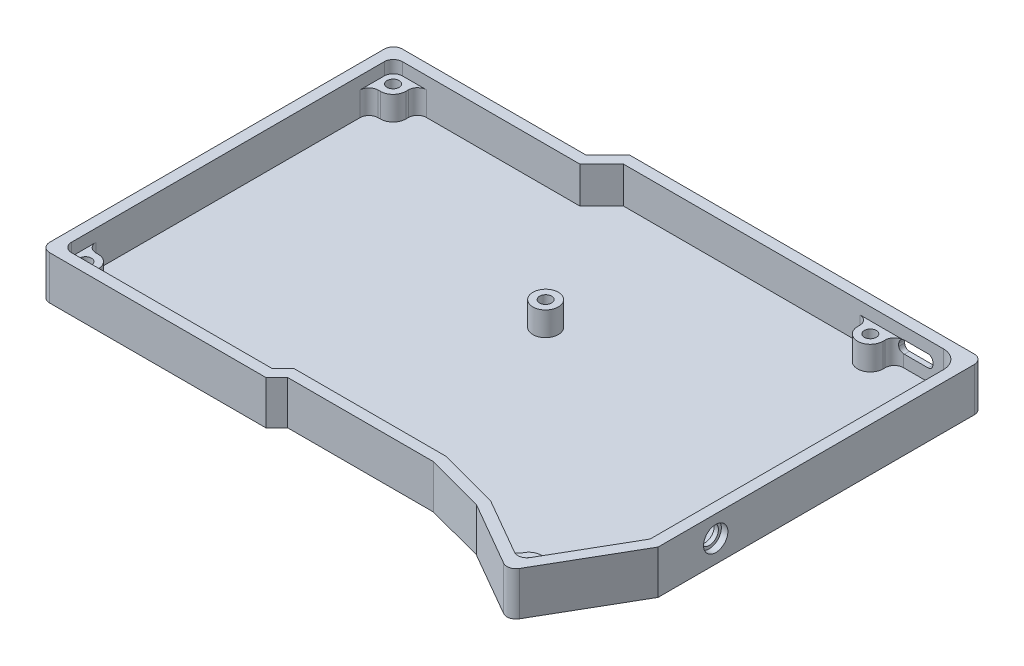
SolidWorks part; units mm, degrees
ref_plane "Front Plane" through (0, 0, 0) normal (0, 0, 1) x (1, 0, 0)
ref_plane "Top Plane" through (0, 0, 0) normal (0, 1, 0) x (1, 0, 0)
ref_plane "Right Plane" through (0, 0, 0) normal (1, 0, 0) x (0, 0, -1)
sketch "Sketch1" plane through (0, 0, 0) normal (0, 1, 0) x (1, 0, 0)
  line L0 (74.625, 48) -> (-17.625, 48) construction
  line L1 (-74.625, -48) -> (74.625, -48) construction
  line L2 (-74.625, -48) -> (-74.625, 48) construction
  line L3 (-74.625, 48) -> (74.625, 48) construction
  line L4 (74.625, -48) -> (74.625, 48) construction
  line L5 (-74.625, -48) -> (74.625, 48) construction
  line L6 (-74.625, 48) -> (74.625, -48) construction
  line L7 (-17.625, 48) -> (-17.625, 42) construction
  line L8 (-17.625, 42) -> (-23.625, 42) construction
  line L9 (-17.625, 48) -> (-23.625, 42) construction
  line L10 (-23.625, 42) -> (-74.625, 42) construction
  line L11 (-74.625, 42) -> (-74.625, -48) construction
  line L12 (-74.625, -48) -> (-17.625, -48) construction
  line L13 (-17.625, -48) -> (-17.625, -45) construction
  line L14 (-17.625, -45) -> (-14.625, -45) construction
  line L15 (-14.625, -45) -> (-17.625, -48) construction
  line L16 (-14.625, -45) -> (27.375, -45) construction
  line L17 (74.625, 48) -> (74.625, -37) construction
  line L18 (27.375, -45) -> (44.3045, -45) construction
  line L19 (44.3045, -45) -> (44.3045, -49.5167) construction
  line L20 (44.3045, -49.5167) -> (27.375, -45) construction
  line L21 (44.3045, -49.5167) -> (61.6269, -49.5167) construction
  line L22 (61.6269, -49.5167) -> (61.6269, -59.5048) construction
  line L23 (44.3045, -49.5167) -> (61.6269, -59.5048) construction
  line L24 (74.625, -37) -> (61.6269, -59.5048) construction
  line L25 (75.125, -37.134) -> (61.81, -60.1875)
  line L26 (44.1119, -49.9828) -> (61.81, -60.1875)
  line L27 (44.1119, -49.9828) -> (27.3094, -45.5)
  line L28 (-14.4179, -45.5) -> (27.3094, -45.5)
  line L29 (-14.4179, -45.5) -> (-17.4179, -48.5)
  line L30 (-75.125, -48.5) -> (-17.4179, -48.5)
  line L31 (-75.125, 42.5) -> (-75.125, -48.5)
  line L32 (-23.8321, 42.5) -> (-75.125, 42.5)
  line L33 (-17.8321, 48.5) -> (-23.8321, 42.5)
  line L34 (75.125, 48.5) -> (-17.8321, 48.5)
  line L35 (75.125, 48.5) -> (75.125, -37.134)
  line L36 (78.125, -37.9381) -> (62.9085, -64.2839)
  line L37 (42.9562, -52.7794) -> (62.9085, -64.2839)
  line L38 (42.9562, -52.7794) -> (26.9161, -48.5)
  line L39 (-13.1753, -48.5) -> (26.9161, -48.5)
  line L40 (-13.1753, -48.5) -> (-16.1753, -51.5)
  line L41 (-78.125, -51.5) -> (-16.1753, -51.5)
  line L42 (-78.125, 45.5) -> (-78.125, -51.5)
  line L43 (-25.0747, 45.5) -> (-78.125, 45.5)
  line L44 (-19.0747, 51.5) -> (-25.0747, 45.5)
  line L45 (78.125, 51.5) -> (-19.0747, 51.5)
  line L46 (78.125, 51.5) -> (78.125, -37.9381)
  point P0 (0, 0)
  dimension "D1" = 149.25
  dimension "D2" = 96
  dimension "D3" = 92.25
  dimension "D4" = 6
  dimension "D5" = 6
  dimension "D6" = 57
  dimension "D7" = 3
  dimension "D8" = 3
  dimension "D9" = 42
  dimension "D10" = 85
  dimension "D11" = 16.9295
  dimension "D12" = 4.5167
  dimension "D13" = 17.3224
  dimension "D14" = 9.9881
  dimension "D15" = 0.5
  dimension "D16" = 3
extrude "Boss-Extrude1" add sketch "Sketch1" along normal blind 10
sketch "Sketch2" plane through (0, 0, 0) normal (0, -1, 0) x (1, 0, 0)
  line L11 (78.125, -51.5) -> (78.125, 37.9381)
  line L12 (78.125, 37.9381) -> (62.9085, 64.2839)
  line L13 (62.9085, 64.2839) -> (42.9562, 52.7794)
  line L14 (42.9562, 52.7794) -> (26.9161, 48.5)
  line L15 (26.9161, 48.5) -> (-13.1753, 48.5)
  line L16 (-13.1753, 48.5) -> (-16.1753, 51.5)
  line L17 (-16.1753, 51.5) -> (-78.125, 51.5)
  line L18 (-78.125, 51.5) -> (-78.125, -45.5)
  line L19 (-78.125, -45.5) -> (-25.0747, -45.5)
  line L20 (-25.0747, -45.5) -> (-19.0747, -51.5)
  line L21 (-19.0747, -51.5) -> (78.125, -51.5)
  line L22 (78.125, -51.5) -> (78.125, 37.9381)
  line L23 (78.125, 37.9381) -> (62.9085, 64.2839)
  line L24 (62.9085, 64.2839) -> (42.9562, 52.7794)
  line L25 (42.9562, 52.7794) -> (26.9161, 48.5)
  line L26 (26.9161, 48.5) -> (-13.1753, 48.5)
  line L27 (-13.1753, 48.5) -> (-16.1753, 51.5)
  line L28 (-16.1753, 51.5) -> (-78.125, 51.5)
  line L29 (-78.125, 51.5) -> (-78.125, -45.5)
  line L30 (-78.125, -45.5) -> (-25.0747, -45.5)
  line L31 (-25.0747, -45.5) -> (-19.0747, -51.5)
  line L32 (-19.0747, -51.5) -> (78.125, -51.5)
  dimension "D1" = 0
extrude "Boss-Extrude2" add sketch "Sketch2" along normal blind 2
fillet "Fillet1" radius 2.5 3 edges at (-75.125, 5, 48.5) (61.81, 5, 60.1875) (-75.125, 5, -42.5)
fillet "Fillet2" radius 2.5 4 edges at (-78.125, 4, 51.5) (62.9085, 4, 64.2839) (78.125, 4, -51.5) (-78.125, 4, -45.5)
fillet "Fillet4" radius 5 1 edges at (75.125, 5, -48.5)
sketch "Sketch3" plane through (0, 0, 0) normal (0, 1, 0) x (1, 0, 0)
  line L0 (-68.5, 39.3) -> (-68.5, 42.5)
  line L1 (-72, 35.8) -> (-75.125, 35.8)
  line L2 (-72, -41.8) -> (-75.125, -41.8)
  line L3 (-68.5, -45.3) -> (-68.5, -48.5)
  line L4 (-75.125, -41.8) -> (-75.125, -46)
  line L5 (-72.625, -48.5) -> (-68.5, -48.5)
  line L6 (-70.5823, 42.5) -> (-68.5, 42.5)
  line L7 (-75.125, 35.8) -> (-75.125, 37.7238)
  line L8 (60.7118, -55.9182) -> (-24914.9904, -43371.2077) construction
  line L9 (61.0782, -56.2838) -> (43376.3677, -25031.986) construction
  line L10 (62.3933, -53.0019) -> (65.0679, -54.5467)
  line L11 (-75.125, 40) -> (-75.125, -46)
  line L12 (-72.625, -48.5) -> (-17.4179, -48.5)
  line L13 (-17.4179, -48.5) -> (-14.4179, -45.5)
  line L14 (-14.4179, -45.5) -> (27.3094, -45.5)
  line L15 (27.3094, -45.5) -> (44.1119, -49.9828)
  line L16 (44.1119, -49.9828) -> (59.6458, -58.9397)
  line L17 (63.0594, -58.0242) -> (75.125, -37.134)
  line L18 (75.125, -37.134) -> (75.125, 43.5)
  line L19 (70.125, 48.5) -> (-17.8321, 48.5)
  line L20 (-17.8321, 48.5) -> (-23.8321, 42.5)
  line L21 (-23.8321, 42.5) -> (-72.625, 42.5)
  line L22 (-75.125, 40) -> (-75.125, -46) construction
  line L23 (-72.625, -48.5) -> (-17.4179, -48.5) construction
  line L24 (-17.4179, -48.5) -> (-14.4179, -45.5) construction
  line L25 (-14.4179, -45.5) -> (27.3094, -45.5) construction
  line L26 (27.3094, -45.5) -> (44.1119, -49.9828) construction
  line L27 (44.1119, -49.9828) -> (59.6458, -58.9397) construction
  line L28 (63.0594, -58.0242) -> (75.125, -37.134) construction
  line L29 (75.125, -37.134) -> (75.125, 43.5) construction
  line L30 (70.125, 48.5) -> (-17.8321, 48.5) construction
  line L31 (-17.8321, 48.5) -> (-23.8321, 42.5) construction
  line L32 (-23.8321, 42.5) -> (-72.625, 42.5) construction
  line L33 (57.6129, -54.2857) -> (56.1063, -56.8987)
  line L34 (56.1063, -56.8987) -> (59.6458, -58.9397)
  line L35 (63.0594, -58.0242) -> (65.0679, -54.5467)
  line L36 (56.645, 45.4) -> (56.645, 48.5)
  line L37 (49.645, 48.5) -> (51.5202, 48.5)
  line L38 (49.645, 48.5) -> (49.645, 45.4)
  line L39 (57.6003, -57.7602) -> (56.1063, -56.8987)
  circle A0 centre (-72, 39.3) radius 3.5
  circle A1 centre (-72, -45.3) radius 3.5
  circle A2 centre (60.645, -56.034) radius 3.5
  circle A3 centre (53.145, 45.4) radius 3.5
  arc A4 (-75.125, -46) -> (-72.625, -48.5) centre (-72.625, -46) ccw
  arc A5 (59.6458, -58.9397) -> (63.0594, -58.0242) centre (60.8946, -56.7739) ccw
  arc A7 (-72.625, 42.5) -> (-75.125, 40) centre (-72.625, 40) ccw
  arc A8 (-75.125, -46) -> (-72.625, -48.5) centre (-72.625, -46) ccw
  arc A9 (59.6458, -58.9397) -> (63.0594, -58.0242) centre (60.8946, -56.7739) ccw
  arc A11 (-72.625, 42.5) -> (-75.125, 40) centre (-72.625, 40) ccw
  circle A12 centre (0.325, 8.92) radius 3.5
  arc A16 (75.125, 43.5) -> (70.125, 48.5) centre (70.125, 43.5) ccw
  arc A17 (75.125, 43.5) -> (70.125, 48.5) centre (70.125, 43.5) ccw
  point P35 (62.3933, -53.0019)
  point P39 (58.8967, -59.0661)
  point P43 (57.6129, -54.2857)
  point P53 (57.6003, -57.7602)
  line M22 (-75.125, 40) -> (-75.125, -46)
  arc M23 (-75.125, -46) -> (-72.625, -48.5) centre (-72.625, -46) ccw
  line M24 (-72.625, -48.5) -> (-17.4179, -48.5)
  line M28 (44.1119, -49.9828) -> (59.6458, -58.9397)
  arc M29 (59.6458, -58.9397) -> (63.0594, -58.0242) centre (60.8946, -56.7739) ccw
  line M30 (63.0594, -58.0242) -> (75.125, -37.134)
  line M33 (70.125, 48.5) -> (-17.8321, 48.5)
  line M35 (-23.8321, 42.5) -> (-72.625, 42.5)
  arc M36 (-72.625, 42.5) -> (-75.125, 40) centre (-72.625, 40) ccw
  dimension "D2" = 7
  dimension "D3" = 7
  dimension "D4" = 7
  dimension "D5" = 7
  dimension "D15" = 7
  dimension "D6" = 3.125
  dimension "D7" = 3.2
  dimension "D8" = 3.2
  dimension "D9" = 3.125
  dimension "D10" = 14.48
  dimension "D11" = 18.9
  dimension "D12" = 3.1
  dimension "D13" = 21.98
  dimension "D16" = 75.45
  dimension "D17" = 33.58
  dimension "D1" = 0
extrude "Boss-Extrude3" add sketch "Sketch3" along normal blind 6.6 contours A1 L4 M24 M23 | A1 L2 M22 | A0 L0 M35 | A0 M35 M36 M22 | A0 L1 M22 | A12 | A3 M33 | A3 L36 M33 | A3 L38 M33 | A2 L35 L10 | A2 L34 M30 M29 | A2 L33 M28 | A1 L5 L3 region at (-69.0716, 0, -41.7549) region at (-71.9115, 0, -39.2309) region at (64.1821, 0, 54.6307) region at (-74.3929, 0, -36.334) region at (-74.3929, 0, 42.334) region at (50.1671, 0, -47.7724) region at (-71.9115, 0, 45.2309) region at (53.145, 0, -45.324) region at (-69.0716, 0, 47.7549) region at (56.1229, 0, -47.7724) region at (56.8818, 0, 56.524) region at (60.6094, 0, 55.8481) region at (0.325, 0, -8.92)
sketch "Sketch5" plane through (0, 6.6, 0) normal (0, 1, 0) x (1, 0, 0)
  arc A0 (49.645, 45.4) -> (56.645, 45.4) centre (53.145, 45.4) ccw construction
  arc A1 (62.3933, -53.0019) -> (57.6129, -54.2857) centre (60.645, -56.034) ccw construction
  arc A2 (-68.5, -45.3) -> (-72, -41.8) centre (-72, -45.3) ccw construction
  circle A3 centre (0.325, 8.92) radius 3.5 construction
  arc A4 (-72, 35.8) -> (-68.5, 39.3) centre (-72, 39.3) ccw construction
  arc A5 (49.645, 45.4) -> (56.645, 45.4) centre (53.145, 45.4) ccw construction
  arc A6 (62.3933, -53.0019) -> (57.6129, -54.2857) centre (60.645, -56.034) ccw construction
  arc A7 (-68.5, -45.3) -> (-72, -41.8) centre (-72, -45.3) ccw construction
  circle A8 centre (0.325, 8.92) radius 3.5 construction
  arc A9 (-72, 35.8) -> (-68.5, 39.3) centre (-72, 39.3) ccw construction
  circle A10 centre (-72, 39.3) radius 1.65
  circle A11 centre (0.325, 8.92) radius 1.65
  circle A12 centre (53.145, 45.4) radius 1.65
  circle A13 centre (60.645, -56.034) radius 1.65
  circle A14 centre (-72, -45.3) radius 1.65
  dimension "D1" = 3.3
  dimension "D2" = 3.3
  dimension "D3" = 3.3
  dimension "D4" = 3.3
  dimension "D5" = 3.3
extrude "Cut-Extrude1" cut sketch "Sketch5" against normal blind 2.5
fillet "Fillet3" radius 2.5 8 edges at (65.0679, 3.3, 54.5467) (49.645, 3.3, -48.5) (56.645, 3.3, -48.5) (-75.125, 3.3, -35.8) (-68.5, 3.3, -42.5) (-75.125, 3.3, 41.8) (56.1063, 3.3, 56.8987) (-68.5, 3.3, 48.5)
sketch "Sketch6" plane through (75.125, 0, 0) normal (-1, 0, 0) x (0, 0, 1)
  line L0 (37.134, 10) -> (37.134, 0) construction
  line L1 (37.134, 0) -> (-43.5, 0) construction
  circle A0 centre (22.0991, 4.1) radius 2.55
  dimension "D1" = 5.1
  dimension "D2" = 15.0349
  dimension "D3" = 4.1
extrude "Cut-Extrude2" cut sketch "Sketch6" against normal through all
sketch "Sketch7" plane through (78.125, 0, 0) normal (1, 0, 0) x (0, 0, -1)
  circle A0 centre (-22.0991, 4.1) radius 3.35
  dimension "D1" = 6.7
extrude "Cut-Extrude3" cut sketch "Sketch7" against normal blind 1.8
sketch "Sketch8" plane through (0, 0, -51.5) normal (0, 0, -1) x (-1, 0, 0)
  line L0 (-75.625, 10) -> (-75.625, -2) construction
  line L1 (-67.23, 3.34) -> (-58.09, 3.34)
  line L2 (-67.23, 3.34) -> (-67.23, 6.7)
  line L3 (-67.23, 6.7) -> (-58.09, 6.7)
  line L4 (-58.09, 3.34) -> (-58.09, 6.7)
  line L5 (-67.23, 3.34) -> (-58.09, 6.7) construction
  line L6 (-67.23, 6.7) -> (-58.09, 3.34) construction
  line L7 (19.0747, -2) -> (-75.625, -2) construction
  point P0 (-62.66, 5.02)
  dimension "D1" = 3.36
  dimension "D2" = 9.14
  dimension "D3" = 8.395
  dimension "D4" = 5.34
extrude "Cut-Extrude4" cut sketch "Sketch8" against normal up to next
fillet "Fillet5" radius 1.3 4 edges at (67.23, 3.34, -50) (58.09, 3.34, -49.8832) (58.09, 6.7, -50) (67.23, 6.7, -50)
sketch "Sketch9" plane through (0, 0, -51.5) normal (0, 0, -1) x (-1, 0, 0)
  line L0 (-67.23, 5.4) -> (-67.23, 4.64) construction
  line L1 (-65.93, 3.34) -> (-59.39, 3.34) construction
  line L2 (-58.09, 4.64) -> (-58.09, 5.4) construction
  line L3 (-59.39, 6.7) -> (-65.93, 6.7) construction
  line L4 (-67.23, 5.4) -> (-67.23, 4.64) construction
  line L5 (-65.93, 3.34) -> (-59.39, 3.34) construction
  line L6 (-58.09, 4.64) -> (-58.09, 5.4) construction
  line L7 (-59.39, 6.7) -> (-65.93, 6.7) construction
  line L8 (-69.73, 5.4) -> (-69.73, 4.64)
  line L9 (-65.93, 0.84) -> (-59.39, 0.84)
  line L10 (-55.59, 4.64) -> (-55.59, 5.4)
  line L11 (-59.39, 9.2) -> (-65.93, 9.2)
  arc A0 (-65.93, 6.7) -> (-67.23, 5.4) centre (-65.93, 5.4) ccw construction
  arc A1 (-67.23, 4.64) -> (-65.93, 3.34) centre (-65.93, 4.64) ccw construction
  arc A2 (-59.39, 3.34) -> (-58.09, 4.64) centre (-59.39, 4.64) ccw construction
  arc A3 (-58.09, 5.4) -> (-59.39, 6.7) centre (-59.39, 5.4) ccw construction
  arc A4 (-65.93, 6.7) -> (-67.23, 5.4) centre (-65.93, 5.4) ccw construction
  arc A5 (-67.23, 4.64) -> (-65.93, 3.34) centre (-65.93, 4.64) ccw construction
  arc A6 (-59.39, 3.34) -> (-58.09, 4.64) centre (-59.39, 4.64) ccw construction
  arc A7 (-58.09, 5.4) -> (-59.39, 6.7) centre (-59.39, 5.4) ccw construction
  arc A8 (-69.73, 4.64) -> (-65.93, 0.84) centre (-65.93, 4.64) ccw
  arc A9 (-59.39, 0.84) -> (-55.59, 4.64) centre (-59.39, 4.64) ccw
  arc A10 (-55.59, 5.4) -> (-59.39, 9.2) centre (-59.39, 5.4) ccw
  arc A11 (-65.93, 9.2) -> (-69.73, 5.4) centre (-65.93, 5.4) ccw
  dimension "D1" = 2.5
extrude "Cut-Extrude5" cut sketch "Sketch9" against normal blind 1.6 contours L8 A8 L9 A9 L10 A10 L11 A11
